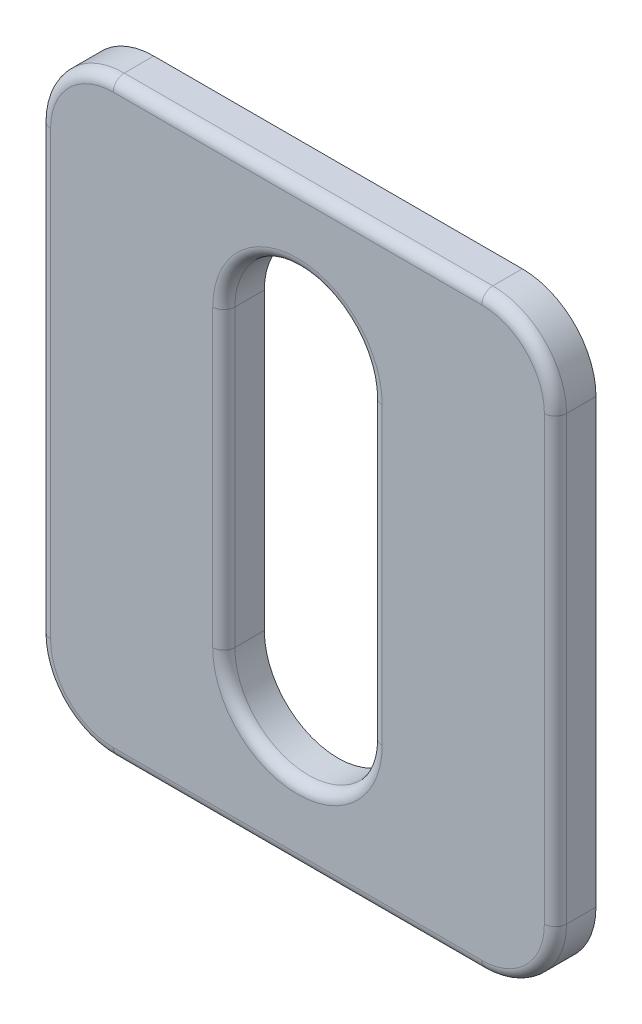
SolidWorks part; units mm, degrees
material "ABS"
ref_plane "Front Plane" through (0, 0, 0) normal (0, 0, 1) x (1, 0, 0)
ref_plane "Top Plane" through (0, 0, 0) normal (0, 1, 0) x (1, 0, 0)
ref_plane "Right Plane" through (0, 0, 0) normal (1, 0, 0) x (0, 0, -1)
sketch "Sketch1" plane through (0, 0, 0) normal (0, 0, 1) x (1, 0, 0)
  line L0 (17.5, 40) -> (17.5, 20) construction
  line L1 (0, 0) -> (35, 0)
  line L2 (0, 0) -> (0, 40)
  line L3 (0, 40) -> (35, 40)
  line L4 (35, 0) -> (35, 40)
  line L5 (17.5, 20) -> (17.5, 0) construction
  line L6 (17.5, 30) -> (17.5, 10) construction
  line L7 (22.5, 30) -> (22.5, 10)
  line L8 (12.5, 30) -> (12.5, 10)
  arc A0 (22.5, 30) -> (12.5, 30) centre (17.5, 30) ccw
  arc A1 (12.5, 10) -> (22.5, 10) centre (17.5, 10) ccw
  point P10 (17.5, 20)
  dimension "D3" = 5
  dimension "D1" = 35
  dimension "D2" = 40
extrude "Boss-Extrude1" add sketch "Sketch1" along normal blind 2.75
fillet "Fillet1" radius 5 4 edges at (35, 40, 1.375) (35, 0, 1.375) (0, 0, 1.375) (0, 40, 1.375)
fillet "Fillet2" radius 0.75 12 edges at (1.4645, 1.4645, 2.75) (0, 20, 2.75) (1.4645, 38.5355, 2.75) (33.5355, 38.5355, 2.75) (17.5, 40, 2.75) (35, 20, 2.75) (33.5355, 1.4645, 2.75) (17.5, 0, 2.75) (17.5, 5, 2.75) (22.5, 20, 2.75) (17.5, 35, 2.75) (12.5, 20, 2.75)
